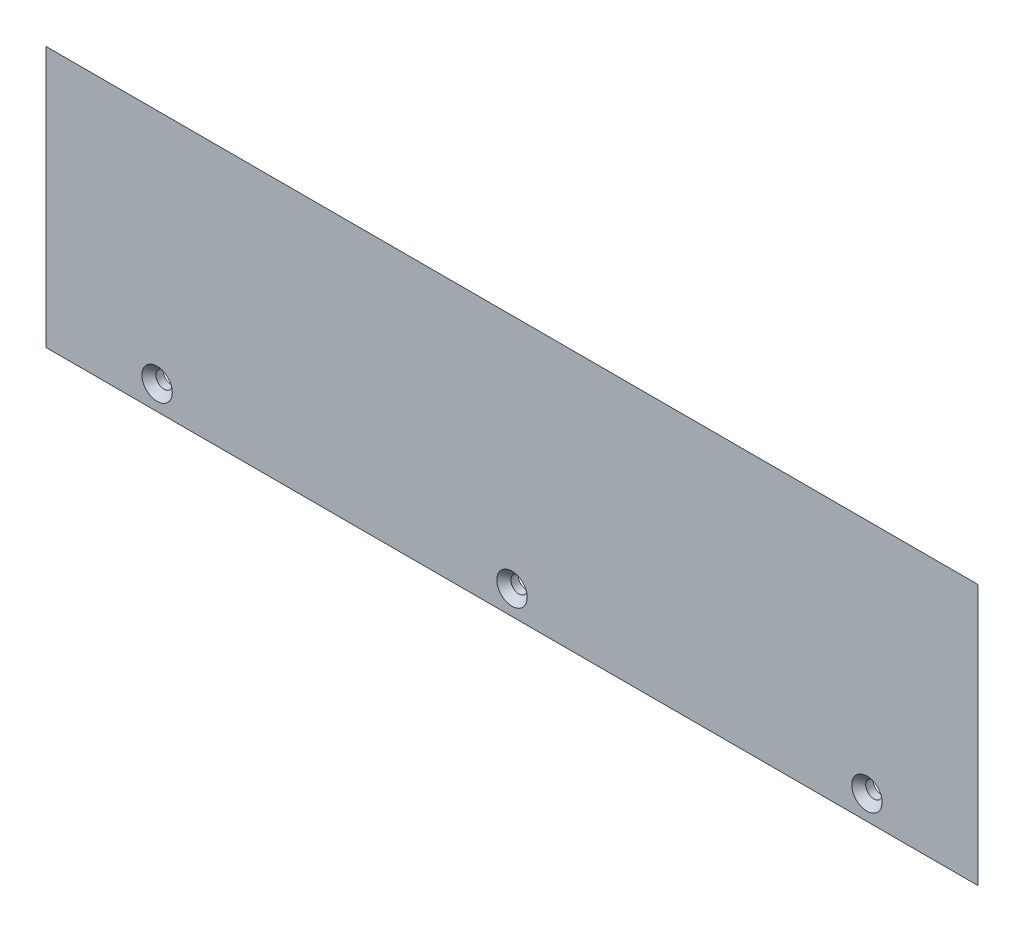
SolidWorks part; units mm, degrees
ref_plane "Front Plane" through (0, 0, 0) normal (0, 0, 1) x (1, 0, 0)
ref_plane "Top Plane" through (0, 0, 0) normal (0, 1, 0) x (1, 0, 0)
ref_plane "Right Plane" through (0, 0, 0) normal (1, 0, 0) x (0, 0, -1)
sketch "Sketch1" plane through (0, 0, 0) normal (0, 0, 1) x (1, 0, 0)
  line L1 (0, 0) -> (193, 0)
  line L2 (0, 0) -> (0, 54)
  line L3 (0, 54) -> (193, 54)
  line L4 (193, 0) -> (193, 54)
  dimension "D1" = 54
  dimension "D2" = 193
extrude "Boss-Extrude1" add sketch "Sketch1" along normal blind 3
chamfer "Chamfer1" distance 3 angle 45 3 edges at (0, 27, 0) (96.5, 54, 0) (193, 27, 0)
sketch "Sketch2" plane through (0, 0, 3) normal (0, 0, 1) x (1, 0, 0)
  line L0 (0, 5) -> (193, 5) construction
  line L1 (0, 54) -> (0, 0) construction
  line L2 (193, 0) -> (193, 54) construction
  line L3 (0, 0) -> (193, 0) construction
  circle A0 centre (23, 5) radius 2
  circle A1 centre (170, 5) radius 2
  circle A2 centre (96.5, 5) radius 2
  dimension "D2" = 4
  dimension "D1" = 5
  dimension "D3" = 23
  dimension "D4" = 23
hole_wizard "CSK for M3 Flat Head Machine Screw1" positions "Sketch4" profile "Sketch3" countersink size "M3" standard "ANSI Metric" end condition through all
sketch "Sketch4" plane through (0, 0, 3) normal (0, 0, 1) x (1, 0, 0)
  point P0 (23, 5)
  point P3 (96.5, 5)
  point P6 (170, 5)
sketch "Sketch3" plane through (23, 5, 3) normal (1, 0, 0) x (0, -1, 0)
  line L0 (0, 0) -> (0, 3)
  line L1 (0, 3) -> (1.7, 3)
  line L2 (1.7, 3) -> (1.7, 1.45)
  line L3 (1.7, 1.45) -> (3.15, 0)
  line L5 (3.15, 0) -> (0, 0)
  line L6 (-1.7, 1.45) -> (-3.15, 0) construction
  line L11 (0, -6.35) -> (0, 107.95) construction
  dimension "Thru Hole Dia." = 3.4
  dimension "Thru Hole Depth" = 3
  dimension "Near C'Sink Dia." = 6.3
  dimension "Near C'Sink Angle" = 90
